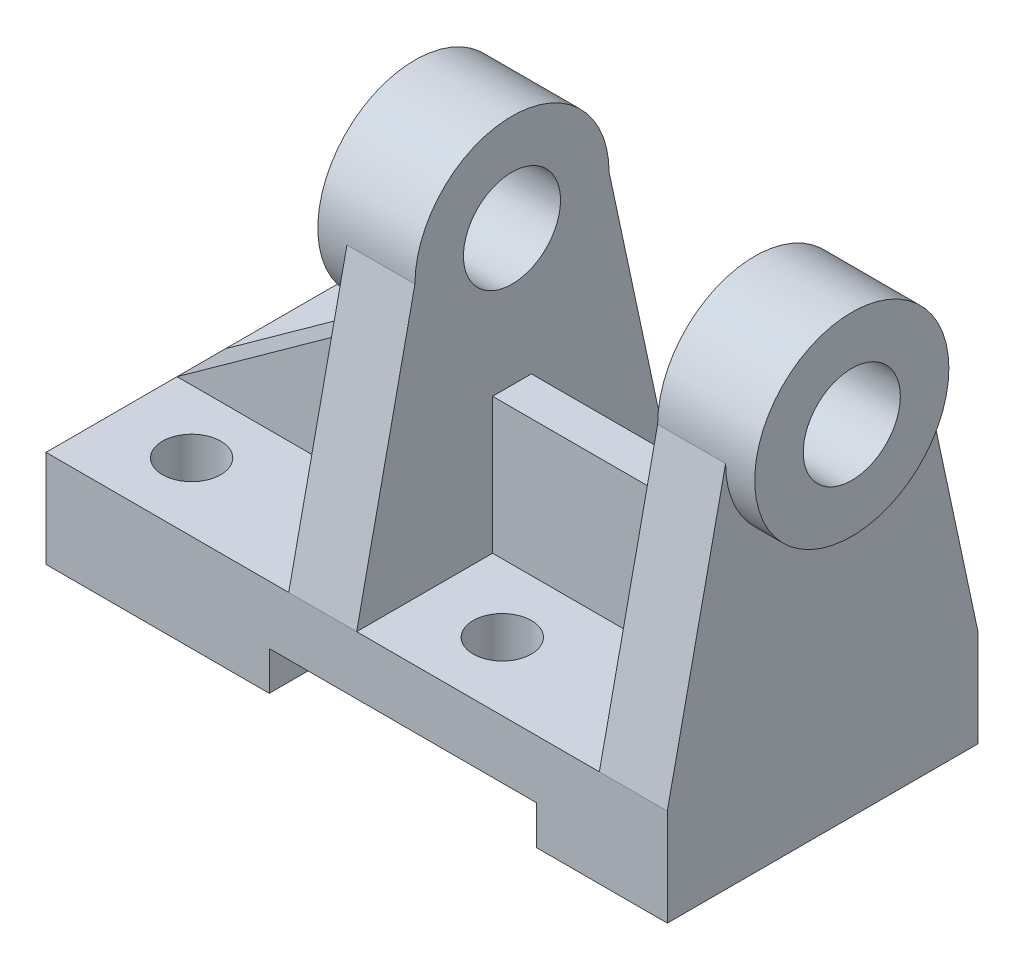
SolidWorks part; units mm, degrees
ref_plane "Front Plane" through (0, 0, 0) normal (0, 0, 1) x (1, 0, 0)
ref_plane "Top Plane" through (0, 0, 0) normal (0, 1, 0) x (1, 0, 0)
ref_plane "Right Plane" through (0, 0, 0) normal (1, 0, 0) x (0, 0, -1)
sketch "Sketch1" plane through (0, 0, 0) normal (0, 1, 0) x (1, 0, 0)
  line L1 (-64, -32) -> (64, -32)
  line L2 (-64, -32) -> (-64, 32)
  line L3 (-64, 32) -> (64, 32)
  line L4 (64, -32) -> (64, 32)
  line L5 (-64, -32) -> (64, 32) construction
  line L6 (-64, 32) -> (64, -32) construction
  point P0 (0, 0)
  dimension "D1" = 128
  dimension "D2" = 64
extrude "Boss-Extrude1" add sketch "Sketch1" along normal blind 20
sketch "Sketch2" plane through (0, 0, 32) normal (0, 0, 1) x (1, 0, 0)
  line L0 (-64, 0) -> (64, 0) construction
  line L1 (-18, 0) -> (37, 0)
  line L2 (-18, 0) -> (-18, 8)
  line L3 (-18, 8) -> (37, 8)
  line L4 (37, 0) -> (37, 8)
  dimension "D1" = 27
  dimension "D2" = 8
  dimension "D3" = 55
extrude "Cut-Extrude1" cut sketch "Sketch2" against normal through all
sketch "Sketch4" plane through (64, 0, 0) normal (1, 0, 0) x (0, 0, -1)
  line L0 (-32, 20) -> (32, 20) construction
  line L1 (-20, 76) -> (-32, 20)
  line L2 (20, 76) -> (32, 20)
  circle A0 centre (0, 76) radius 20
  circle A1 centre (0, 76) radius 10
  line M3 (32, 20) -> (-32, 20)
  dimension "D1" = 20
  dimension "D2" = 40
  dimension "D3" = 56
extrude "Boss-Extrude3" add sketch "Sketch4" against normal blind 14 contours A0 L1 L2 M3 | A0 A1 region at (64, 39.8852, 0) region at (64, 95.4343, 0)
extrude "Boss-Extrude4" add sketch "Sketch4<3>" along normal blind 6 contours A0 A1 region at (64, 56.5657, 0)
sketch "Sketch4<3>" plane through (64, 0, 0) normal (1, 0, 0) x (0, 0, -1) same geometry as "Sketch4"
ref_plane "Plane1" through (0, 0, 0) normal (-1, 0, 0) x (0, 0, 1)
ref_plane "Plane2" through (25, 0, 0) normal (-1, 0, 0) x (0, 0, 1)
mirror "Mirror2" about plane through (25, 0, 0) normal (-1, 0, 0) of "Boss-Extrude4", "Boss-Extrude3"
sketch "Sketch18" plane through (0, 20, 0) normal (0, 1, 0) x (1, 0, 0)
  line L5 (50, 20) -> (50, -20) construction
  line L6 (0, -4) -> (50, -4)
  line L7 (0, -4) -> (0, 4)
  line L8 (0, 4) -> (50, 4)
  line L9 (50, -4) -> (50, 4)
  line L10 (0, -4) -> (50, 4) construction
  line L11 (0, 4) -> (50, -4) construction
  point P11 (25, 0)
  dimension "D1" = 8
extrude "Boss-Extrude6" add sketch "Sketch18" along normal blind 28
sketch "Sketch19" plane through (0, 0, 0) normal (0, 0, 1) x (1, 0, 0)
  line L0 (-64, 20) -> (-14, 56)
rib "Rib1" sketch "Sketch19" sketch "Sketch19" thickness 10 extrusion direction parallel to sketch draft on no parameters "D1"=10
sketch "Sketch20" plane through (0, 20, 0) normal (0, 1, 0) x (1, 0, 0)
  line L0 (50, -4) -> (50, -32) construction
  line L1 (0, -32) -> (50, -32) construction
  circle A0 centre (16, -18) radius 6
  dimension "D1" = 12
  dimension "D2" = 34
  dimension "D3" = 14
extrude "Cut-Extrude2" cut sketch "Sketch20" against normal through all
sketch "Sketch21" plane through (0, 20, 0) normal (0, 1, 0) x (1, 0, 0)
  line L0 (50, 32) -> (50, 4) construction
  line L1 (50, 32) -> (0, 32) construction
  circle A0 centre (16, 18) radius 6
  dimension "D1" = 12
  dimension "D2" = 34
  dimension "D3" = 14
extrude "Cut-Extrude3" cut sketch "Sketch21" against normal through all
sketch "Sketch22" plane through (0, 20, 0) normal (0, 1, 0) x (1, 0, 0)
  line L0 (-14, 32) -> (-14, 5) construction
  line L1 (-14, -5) -> (-14, -32) construction
  line L2 (-14, 32) -> (-64, 32) construction
  line L3 (-64, -32) -> (-14, -32) construction
  circle A0 centre (-48, -18) radius 6
  circle A1 centre (-48, 18) radius 6
  dimension "D1" = 12
  dimension "D2" = 12
  dimension "D3" = 34
  dimension "D4" = 34
  dimension "D5" = 14
  dimension "D6" = 14
extrude "Cut-Extrude4" cut sketch "Sketch22" against normal through all
